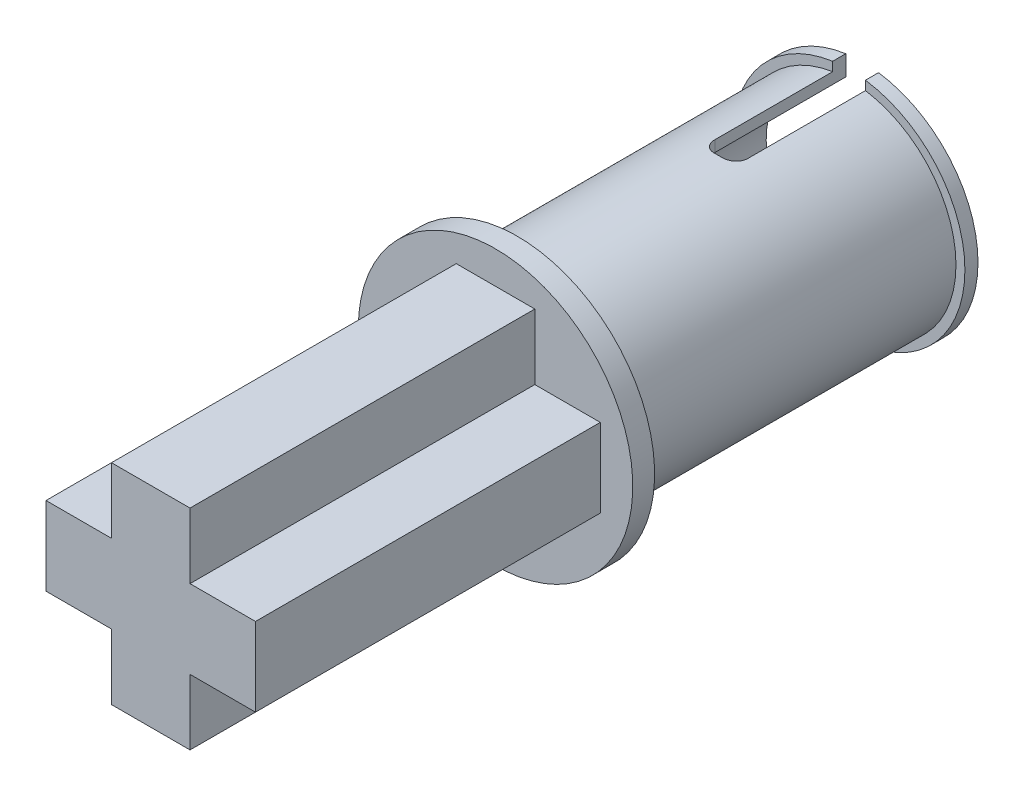
SolidWorks part; units mm, degrees
ref_plane "Front Plane" through (0, 0, 0) normal (0, 0, 1) x (1, 0, 0)
ref_plane "Top Plane" through (0, 0, 0) normal (0, 1, 0) x (1, 0, 0)
ref_plane "Right Plane" through (0, 0, 0) normal (1, 0, 0) x (0, 0, -1)
sketch "Sketch1" plane through (0, 0, 0) normal (0, 0, 1) x (1, 0, 0)
  line L0 (-2.4, 0) -> (2.4, 0)
  line L1 (-2.4, 0.9) -> (-2.4, -0.9)
  line L2 (-2.4, 0.9) -> (-0.9, 0.9)
  line L3 (0, 2.4) -> (0, -2.4)
  line L4 (-0.9, 0.9) -> (-0.9, 2.4)
  line L5 (-0.9, 2.4) -> (0.9, 2.4)
  line L6 (0.9, 0.9) -> (0.9, 2.4)
  line L7 (2.4, 0.9) -> (0.9, 0.9)
  line L8 (2.4, 0.9) -> (2.4, -0.9)
  line L9 (2.4, -0.9) -> (0.9, -0.9)
  line L10 (0.9, -0.9) -> (0.9, -2.4)
  line L11 (-0.9, -2.4) -> (0.9, -2.4)
  line L12 (-0.9, -0.9) -> (-0.9, -2.4)
  line L13 (-2.4, -0.9) -> (-0.9, -0.9)
  point P4 (0, 0)
  point P8 (-2.4, 0)
  point P12 (0, 0)
  dimension "D1" = 4.8
  dimension "D2" = 1.8
  dimension "D3" = 1.5
  dimension "D4" = 4.8
  dimension "D5" = 1.8
extrude "Boss-Extrude1" add sketch "Sketch1" along normal blind 7.9 contours L5 L4 L2 L1 L0 L3 | L1 L13 L12 L11 L3 L0 | L8 L7 L6 L5 L3 L0 | L3 L11 L10 L9 L8 L0 region at (-2.3661, 0.45, 0) region at (-1.2, -0.0339, 0) region at (0.0339, 1.2, 0) region at (1.2, -0.0339, 0)
sketch "Sketch2" plane through (0, 0, 0) normal (0, 0, -1) x (-1, 0, 0)
  circle A0 centre (0, 0) radius 3.1445
extrude "Boss-Extrude3" add sketch "Sketch2" along normal blind 0.5 contours A0
sketch "Sketch3" plane through (0, 0, -0.5) normal (0, 0, -1) x (-1, 0, 0)
  circle A0 centre (0, 0) radius 2.45
  dimension "D1" = 4.9
extrude "Boss-Extrude4" add sketch "Sketch3" along normal blind 7.9
sketch "Sketch4" plane through (0, 0, -8.4) normal (0, 0, -1) x (-1, 0, 0)
  circle A0 centre (0, 0) radius 2.6546
extrude "Boss-Extrude5" add sketch "Sketch4" against normal blind 0.3
sketch "Sketch5" plane through (0, 0, -8.4) normal (0, 0, -1) x (-1, 0, 0)
  circle A0 centre (0, 0) radius 2.1986
extrude "Cut-Extrude1" cut sketch "Sketch5" against normal up to surface (7.9 mm away) up to face at (-2.45, 0, -0.5)
sketch "Sketch6" plane through (0, 0, -8.4) normal (0, 0, -1) x (-1, 0, 0)
  line L0 (0, 0) -> (2.6546, 0) construction
  line L1 (0, 0) -> (0, 2.6546) construction
  line L2 (0.3755, 2.6546) -> (0.3755, 2.1663)
  line L3 (0.3755, 2.6546) -> (-0.3755, 2.6546)
  line L4 (0, 2.6546) -> (0, 2.1663)
  line L5 (0.3755, 2.1663) -> (-0.3755, 2.1663)
  line L6 (-0.3755, 2.6546) -> (-0.3755, 2.1663)
  line L7 (0.3755, -2.6546) -> (0.3755, -2.1663)
  line L8 (0.3755, -2.6546) -> (-0.3755, -2.6546)
  line L9 (-0.3755, -2.6546) -> (-0.3755, -2.1663)
  line L10 (0.3755, -2.1663) -> (-0.3755, -2.1663)
  circle A0 centre (0, 0) radius 2.6546 construction
  circle A1 centre (0, 0) radius 2.1986 construction
  circle M8 centre (0, 0) radius 2.1986
  circle M9 centre (0, 0) radius 2.6546
extrude "Cut-Extrude2" cut sketch "Sketch6" against normal blind 3.3 contours L4 L2 M9 M8 | L6 L4 M9 M8 | L9 L7 M9 M8 region at (-0.1881, 2.4168, -8.4) region at (0.1881, 2.4168, -8.4) region at (0, -2.4168, -8.4)
fillet "Fillet1" radius 0.3 4 edges at (-0.3755, -2.2937, -5.1) (0.3755, -2.2937, -5.1) (-0.3755, 2.2937, -5.1) (0.3755, 2.2937, -5.1)
